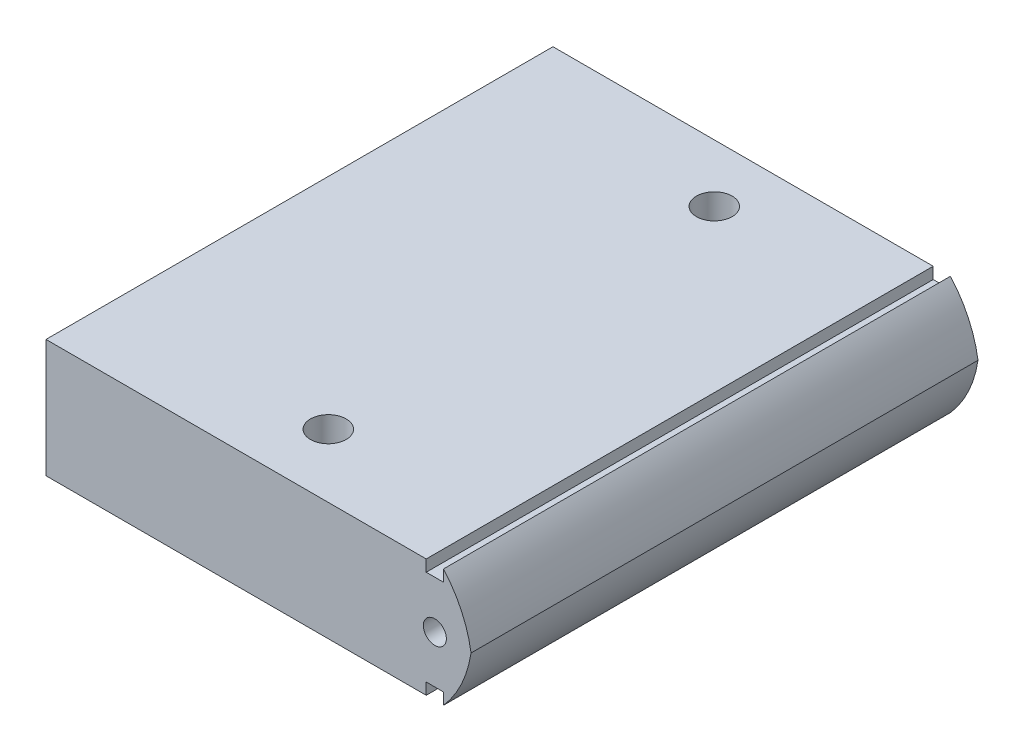
SolidWorks part; units mm, degrees
ref_plane "Alzado" through (0, 0, 0) normal (0, 0, 1) x (1, 0, 0)
ref_plane "Planta" through (0, 0, 0) normal (0, 1, 0) x (1, 0, 0)
ref_plane "Vista lateral" through (0, 0, 0) normal (1, 0, 0) x (0, 0, -1)
sketch "Croquis1" plane through (0, 0, 0) normal (0, 1, 0) x (1, 0, 0)
  line L1 (0, 0) -> (37, 0)
  line L2 (0, 0) -> (0, 44)
  line L3 (0, 44) -> (37, 44)
  line L4 (37, 0) -> (37, 44)
  dimension "D1" = 44
  dimension "D2" = 37
extrude "Saliente-Extruir1" add sketch "Croquis1" along normal blind 10.25
sketch "Croquis2" plane through (0, 10.25, 0) normal (0, 1, 0) x (1, 0, 0)
  line L0 (0, 44) -> (0, 0) construction
  line L1 (37, 44) -> (0, 44) construction
  circle A0 centre (19, 39) radius 1.55
  circle A1 centre (19, 5.5) radius 1.55
  point P6 (19, 2.8498)
  point P7 (0, 0)
  dimension "D2" = 3.1
  dimension "D1" = 19
  dimension "D3" = 33.5
  dimension "D4" = 5
extrude "Cortar-Extruir1" cut sketch "Croquis2" against normal up to surface (10.25 mm away) up to face at (18.5, 0, -22)
sketch "Croquis3" plane through (0, 10.25, 0) normal (0, 1, 0) x (1, 0, 0)
  line L0 (37, 44) -> (0, 44) construction
  line L1 (33, 44) -> (34.5, 44)
  line L2 (33, 44) -> (33, 0)
  line L3 (33, 0) -> (34.5, 0)
  line L4 (34.5, 44) -> (34.5, 0)
  line L5 (0, 0) -> (37, 0) construction
  circle A0 centre (19, 39) radius 1.55 construction
  dimension "D1" = 1.5
  dimension "D2" = 14
extrude "Cortar-Extruir2" cut sketch "Croquis3" against normal blind 1
sketch "Croquis4" plane through (0, 0, 0) normal (0, -1, 0) x (1, 0, 0)
  line L0 (37, -44) -> (0, -44) construction
  line L1 (34.5, -44) -> (33, -44)
  line L2 (34.5, -44) -> (34.5, 0)
  line L3 (34.5, 0) -> (33, 0)
  line L4 (33, -44) -> (33, 0)
  line L5 (0, 0) -> (37, 0) construction
  circle A0 centre (19, -39) radius 1.55 construction
  dimension "D1" = 1.5
  dimension "D2" = 14
extrude "Cortar-Extruir3" cut sketch "Croquis4" against normal blind 1
sketch "Croquis5" plane through (0, 0, -44) normal (0, 0, -1) x (-1, 0, 0)
  line L0 (0, 5.125) -> (-37, 5.125) construction
  line L1 (0, 10.25) -> (0, 0) construction
  line L2 (-37, 10.25) -> (-37, 0) construction
  line L3 (-33.75, 9.25) -> (-33.75, 1) construction
  line L4 (-34.5, 9.25) -> (-33, 9.25) construction
  line L5 (-33, 1) -> (-34.5, 1) construction
  circle A0 centre (-33.75, 5.125) radius 1
  point P14 (-33.75, 5.125)
  dimension "D1" = 2
extrude "Cortar-Extruir4" cut sketch "Croquis5" against normal up to surface (44 mm away) up to face at (28.6667, 5.125, 0)
sketch "Croquis6" plane through (0, 0, 0) normal (-1, 0, 0) x (0, 0, 1)
  line L0 (-44, 10.25) -> (0, 10.25) construction
  line L1 (-34, 9.25) -> (-12, 9.25)
  line L2 (-34, 9.25) -> (-34, 4.25)
  line L3 (-34, 4.25) -> (-12, 4.25)
  line L4 (-12, 9.25) -> (-12, 4.25)
  line L5 (-44, 10.25) -> (-44, 0) construction
  dimension "D1" = 22
  dimension "D2" = 5
  dimension "D3" = 1
  dimension "D4" = 10
extrude "Cortar-Extruir5" cut sketch "Croquis6" against normal blind 5
fillet "Redondeo1" radius 10 2 edges at (37, 0, -22) (37, 10.25, -22)
